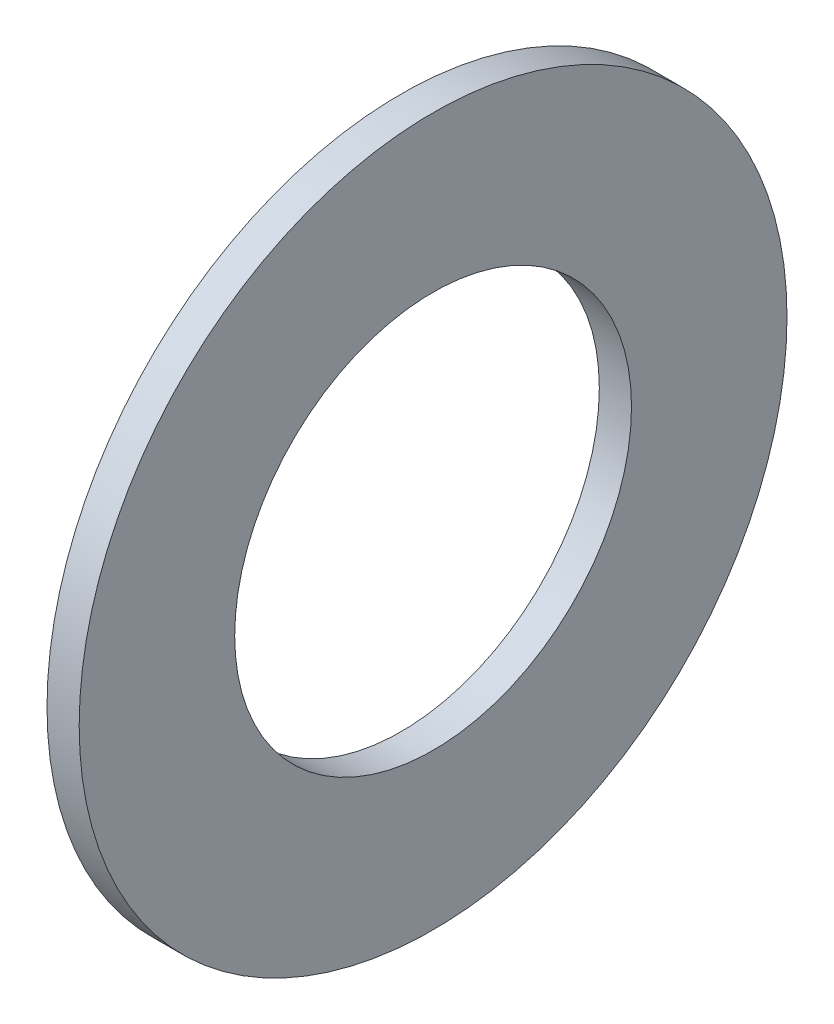
SolidWorks part; units mm, degrees
ref_plane "Plane1" through (0, 0, 0) normal (0, 0, 1) x (1, 0, 0)
ref_plane "Plane2" through (0, 0, 0) normal (0, 1, 0) x (1, 0, 0)
ref_plane "Plane3" through (0, 0, 0) normal (1, 0, 0) x (0, 0, -1)
sketch "Sketch1" plane through (0, 0, 0) normal (0, 0, 1) x (1, 0, 0)
  line L0 (-34.925, 0) -> (9.525, 0) construction
  line L1 (0, 18.5) -> (0, 33)
  line L2 (0, 33) -> (-3, 33)
  line L3 (-3, 33) -> (-3, 18.5)
  line L4 (-3, 18.5) -> (0, 18.5)
  dimension "Thickness" = 3
  dimension "Inside_dia" = 37
  dimension "Outside_dia" = 66
revolve "Base-Revolve" add sketch "Sketch1" angle 360 about L0
